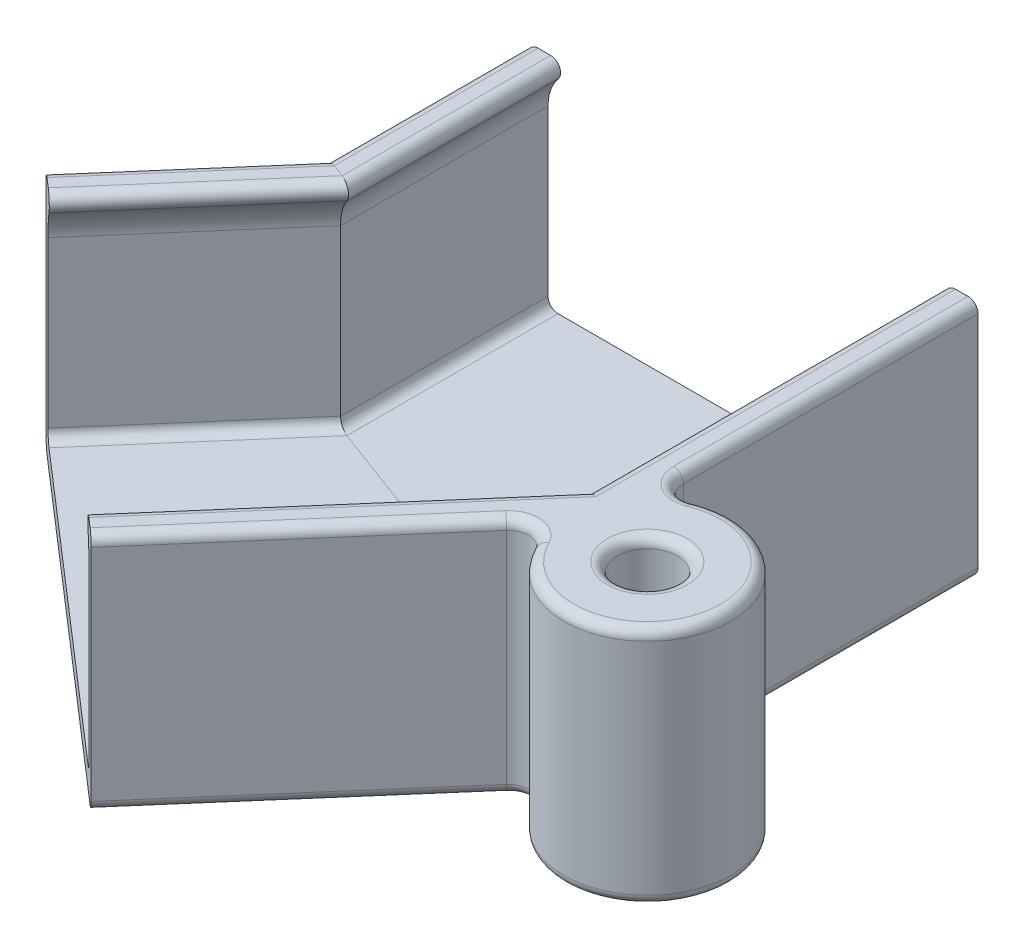
SolidWorks part; units mm, degrees
material "Maple"
ref_plane "Wasteboard" through (0, 0, 0) normal (0, 0, 1) x (1, 0, 0)
ref_plane "Left-Right" through (0, 0, 0) normal (0, 1, 0) x (1, 0, 0)
ref_plane "Front-Back" through (0, 0, 0) normal (1, 0, 0) x (0, 0, -1)
sketch "Sketch1" plane through (0, 0, 0) normal (0, 0, 1) x (1, 0, 0)
  line L0 (-19.5, -12.023) -> (19.5, -12.023)
  line L1 (20.5, -11.023) -> (20.5, 5.477)
  line L2 (20.2426, 9.977) -> (21.5, 9.977)
  line L3 (22.5, 8.977) -> (22.5, -13.023)
  line L4 (21.5, -14.023) -> (-21.5, -14.023)
  line L6 (0, -8.9794) -> (0, 8.6415) construction
  line L10 (-22.5, 8.977) -> (-22.5, -13.023)
  line L12 (-20.5, -11.023) -> (-20.5, 5.477)
  line L13 (-20.2426, 9.977) -> (-21.5, 9.977)
  arc A0 (20.5, 5.477) -> (19.4713, 8.3406) centre (16, 5.477) ccw
  arc A1 (20.2426, 9.977) -> (19.4713, 8.3406) centre (20.2426, 8.977) ccw
  arc A2 (21.5, 9.977) -> (22.5, 8.977) centre (21.5, 8.977) cw
  arc A3 (19.5, -12.023) -> (20.5, -11.023) centre (19.5, -11.023) ccw
  arc A4 (22.5, -13.023) -> (21.5, -14.023) centre (21.5, -13.023) cw
  arc A5 (-22.5, -13.023) -> (-21.5, -14.023) centre (-21.5, -13.023) ccw
  arc A6 (-19.5, -12.023) -> (-20.5, -11.023) centre (-19.5, -11.023) cw
  arc A7 (-21.5, 9.977) -> (-22.5, 8.977) centre (-21.5, 8.977) ccw
  arc A8 (-20.2426, 9.977) -> (-19.4713, 8.3406) centre (-20.2426, 8.977) cw
  arc A9 (-20.5, 5.477) -> (-19.4713, 8.3406) centre (-16, 5.477) cw
  point P0 (-22.5, -14.023)
  point P6 (0, -12.023)
  point P14 (20.5, 5.477)
  point P23 (22.5, -14.023)
  point P40 (0, -14.023)
  dimension "D2" = 9
  dimension "D6" = 1
  dimension "D7" = 1
  dimension "D1" = 22.5
  dimension "D3" = 2
  dimension "D4" = 2
  dimension "D5" = 22
sketch "Sketch3" plane through (0, 0, 0) normal (0, 1, 0) x (1, 0, 0)
  line L0 (0, 0) -> (0, -28.3979)
  line L1 (0, -28.3979) -> (-18.6065, -49.8511)
  line L2 (-22.5, -20) -> (0, -20) construction
  line L3 (-5.5024, -34.7421) -> (-22.5, -20) construction
  dimension "D1" = 20
  dimension "D2" = 40.935
  dimension "D3" = 0
sweep "Sweep1" add profiles "Sketch1" path "Sketch3"
ref_plane "Plane2" through (0, -14.023, 0) normal (0, -1, 0) x (-1, 0, 0)
sketch "Sketch4" plane through (0, -14.023, 0) normal (0, -1, 0) x (-1, 0, 0)
  line L0 (-21.5, -36.4226) -> (-36.8139, -42.1384) construction
  line L1 (-21.5, -36.4226) -> (21.5, -20.3732) construction
  line L3 (-23.5517, -43.059) -> (-22.5, -36.7959) construction
  line L4 (-22.5, -36.7959) -> (-27.3982, -32.7535) construction
  line L5 (-27.3982, -32.7535) -> (-33.3481, -34.9742) construction
  line L6 (-33.3481, -34.9742) -> (-34.3998, -41.2374) construction
  line L7 (-34.3998, -41.2374) -> (-29.5017, -45.2798) construction
  line L8 (-29.5017, -45.2798) -> (-23.5517, -43.059) construction
  line L10 (-21.5, -29.4591) -> (-21.5, -34.6753)
  line L11 (-22.5, -36.7959) -> (1.6089, -64.5933) construction
  line L13 (-21.5, -34.6753) -> (-21.5, -36.4226)
  line L14 (-21.5, -36.4226) -> (-16.9374, -41.6833)
  line L15 (-21.5, -36.4226) -> (2.3643, -63.9381) construction
  line L17 (-21.5, 0) -> (-21.5, -36.4226) construction
  line L18 (-22.5, -29.4591) -> (-21.5, -29.4591)
  line L19 (-17.6929, -42.3385) -> (-16.9374, -41.6833)
  line L20 (-22.5, 0) -> (-22.5, -36.7959) construction
  circle A0 centre (-28.4499, -39.0166) radius 3
  circle A1 centre (-28.4499, -39.0166) radius 5.5 construction
  arc A2 (-25.2639, -31.3074) -> (-20.9919, -42.753) centre (-28.4499, -39.0166) ccw
  arc A3 (-17.6929, -42.3385) -> (-20.9919, -42.753) centre (-19.2038, -43.6489) ccw
  arc A5 (-22.5, -29.4591) -> (-25.2639, -31.3074) centre (-24.5, -29.4591) cw
  point P8 (-34.7412, -33.5392)
  point P9 (0, 0)
  point P19 (0, 0)
  point P30 (-20.1244, -39.5349)
  dimension "D1" = 11
  dimension "D2" = 2
  dimension "D3" = 2
extrude "Boss-Extrude2" add sketch "Sketch4" against normal through all
sketch "Sketch5" plane through (0, -14.023, 0) normal (0, -1, 0) x (-1, 0, 0)
  line L0 (-21.5, -36.4226) -> (-28.4499, -39.0166)
  line L3 (-29.5017, -45.2798) -> (-23.5517, -43.059)
  line L4 (-23.5517, -43.059) -> (-22.5, -36.7959)
  line L5 (-22.5, -36.7959) -> (-27.3982, -32.7535)
  line L6 (-27.3982, -32.7535) -> (-33.3481, -34.9742)
  line L7 (-33.3481, -34.9742) -> (-34.3998, -41.2374)
  line L8 (-34.3998, -41.2374) -> (-29.5017, -45.2798)
  circle A0 centre (-28.4499, -39.0166) radius 5.5 construction
  point P3 (-23.0259, -39.9274)
  dimension "D1" = 11
extrude "Cut-Extrude2" cut sketch "Sketch5" against normal blind 6 draft 2
chamfer "Chamfer1" distance 1 angle 45 6 edges at (30.2999, -8.023, 34.0601) (25.0825, -8.023, 34.9363) (23.2325, -8.023, 39.8927) (26.6, -8.023, 43.9731) (31.8174, -8.023, 43.097) (33.6673, -8.023, 38.1405)
fillet "Fillet8" radius 1 7 edges at (23.3882, -14.023, 31.1215) (23.3882, 9.977, 31.1215) (19.4531, -14.023, 41.6645) (19.4531, 9.977, 41.6645) (36.2649, -14.023, 41.9335) (36.2649, 9.977, 41.9335) (28.4499, 9.977, 36.0166)
